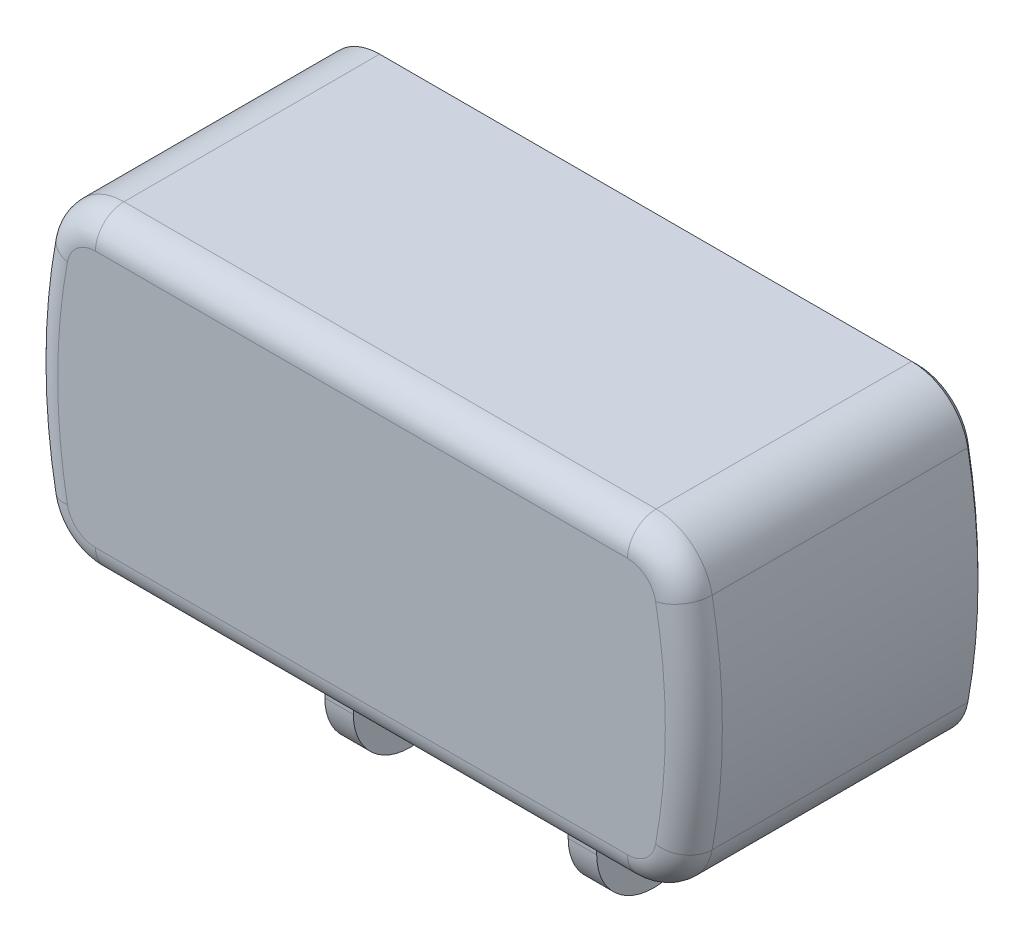
SolidWorks part; units mm, degrees
material "PLA"
ref_plane "Front Plane" through (0, 0, 0) normal (0, 0, 1) x (1, 0, 0)
ref_plane "Top Plane" through (0, 0, 0) normal (0, 1, 0) x (1, 0, 0)
ref_plane "Right Plane" through (0, 0, 0) normal (1, 0, 0) x (0, 0, -1)
sketch "Sketch2" plane through (0, 0, 0) normal (0, 0, 1) x (1, 0, 0)
  line L0 (-47.5, 0) -> (47.5, 0) construction
  line L1 (0, -27.5) -> (0, 27.5) construction
  line L2 (46.625, 27.5) -> (-46.625, 27.5)
  line L3 (46.625, -27.5) -> (-46.625, -27.5)
  arc A0 (-56.4565, 19.3279) -> (-56.4565, -19.3279) centre (47.5, 0) ccw
  arc A1 (-46.625, -27.5) -> (-56.4565, -19.3279) centre (-46.625, -17.5) cw
  arc A2 (-46.625, 27.5) -> (-56.4565, 19.3279) centre (-46.625, 17.5) ccw
  arc A3 (46.625, -27.5) -> (56.4565, -19.3279) centre (46.625, -17.5) ccw
  arc A4 (56.4565, 19.3279) -> (56.4565, -19.3279) centre (-47.5, 0) cw
  arc A5 (46.625, 27.5) -> (56.4565, 19.3279) centre (46.625, 17.5) cw
  point P4 (0, 0)
  point P8 (0, 0)
  dimension "D3" = 0
  dimension "D4" = 10
  dimension "D1" = 95
  dimension "D2" = 55
  dimension "D5" = 46.625
extrude "Boss-Extrude5" add sketch "Sketch2" along normal blind 50.8
fillet "Fillet9" radius 5 8 edges at (-58.238, 0, 50.8) (-53.0172, 25.1902, 50.8) (0, 27.5, 50.8) (53.0172, 25.1902, 50.8) (58.238, 0, 50.8) (53.0172, -25.1902, 50.8) (0, -27.5, 50.8) (-53.0172, -25.1902, 50.8)
sketch "Sketch3" plane through (0, 0, 0) normal (0, 0, -1) x (-1, 0, 0)
  line L0 (-55.738, 0) -> (55.738, 0) construction
  line L1 (0, 0) -> (0, 21.6868) construction
ref_plane "Plane1" through (-18.67, 0, 0) normal (1, 0, 0) x (0, 0, -1)
chamfer "Chamfer1" distance 1 angle 45 8 edges at (0, -27.5, 0) (53.0172, -25.1902, 0) (-53.0172, -25.1902, 0) (58.238, 0, 0) (-58.238, 0, 0) (53.0172, 25.1902, 0) (-53.0172, 25.1902, 0) (0, 27.5, 0)
sketch "Sketch8" plane through (18.825, 0, 0) normal (1, 0, 0) x (0, 0, -1)
  line L2 (-1, -27.5) -> (-45.8, -27.5)
  line L3 (-33.4051, -42.61) -> (-33.4051, -32.61)
  line L4 (-33.4137, -27.5) -> (-38.4137, -27.5)
  line L5 (-38.4137, -27.5) -> (-33.4051, -32.61)
  line L6 (-13.4051, -42.61) -> (-13.4051, -32.61)
  line L7 (-13.4051, -27.5) -> (-8.4051, -27.5)
  line L8 (-8.4051, -27.5) -> (-13.4051, -32.61)
  arc A0 (-33.4051, -42.61) -> (-13.4051, -42.61) centre (-23.4051, -42.61) ccw construction
  arc A2 (-33.4051, -42.61) -> (-13.4051, -42.61) centre (-23.4051, -42.61) ccw
  circle A4 centre (-23.4051, -35.61) radius 1.35
  circle A5 centre (-16.4051, -42.61) radius 1.35
  circle A6 centre (-23.4051, -49.61) radius 1.35
  circle A7 centre (-30.4051, -42.61) radius 1.35
  dimension "D1" = 2.7
  dimension "D2" = 10
  dimension "D3" = 5
  dimension "D4" = 5
extrude "Boss-Extrude6" add sketch "Sketch8" along normal blind 5
mirror "Mirror1" about plane through (0, 0, 0) normal (1, 0, 0) of "Boss-Extrude6"
sketch "Sketch4" plane through (0, 0, 0) normal (0, 0, -1) x (-1, 0, 0)
  line L1 (0, 27.5) -> (0, -27.5) construction
  line L3 (-46.625, 27.5) -> (46.625, 27.5) construction
  line L10 (46.625, -27.5) -> (-46.625, -27.5) construction
  line L11 (-58.238, 0) -> (58.238, 0) construction
  line L13 (-40.665, 14.165) -> (40.665, 14.165)
  line L14 (-45.665, 9.165) -> (-45.665, -9.165)
  line L15 (-40.665, -14.165) -> (40.665, -14.165)
  line L16 (45.665, 9.165) -> (45.665, -9.165)
  arc A0 (-56.4565, 19.3279) -> (-56.4565, -19.3279) centre (47.5, 0) ccw construction
  arc A1 (56.4565, -19.3279) -> (56.4565, 19.3279) centre (-47.5, 0) ccw construction
  arc A2 (40.665, -14.165) -> (45.665, -9.165) centre (40.665, -9.165) ccw
  arc A3 (-45.665, -9.165) -> (-40.665, -14.165) centre (-40.665, -9.165) ccw
  arc A4 (-40.665, 14.165) -> (-45.665, 9.165) centre (-40.665, 9.165) ccw
  arc A5 (40.665, 14.165) -> (45.665, 9.165) centre (40.665, 9.165) cw
  point P18 (0, 14.165)
  point P19 (-45.665, 0)
  point P24 (-45.665, -14.165)
  point P27 (-45.665, 14.165)
  point P30 (45.665, 14.165)
  dimension "D3" = 5
  dimension "D1" = 28.33
  dimension "D2" = 91.33
extrude "Cut-Extrude3" cut sketch "Sketch4" against normal blind 20
chamfer "Chamfer2" distance 20 angle 2 8 edges at (-45.665, 0, 20) (-44.2005, 12.7005, 20) (-44.2005, -12.7005, 20) (0, 14.165, 20) (0, -14.165, 20) (44.2005, 12.7005, 20) (44.2005, -12.7005, 20) (45.665, 0, 20) first distance on face at (-45.665, 0, 10) first distance on face at (-43.6828, 12.1828, 10) first distance on face at (-43.6828, -12.1828, 10) first distance on face at (0, 14.165, 10) first distance on face at (0, -14.165, 10) first distance on face at (43.6828, 12.1828, 10) first distance on face at (43.6828, -12.1828, 10) first distance on face at (45.665, 0, 10)
sketch "Sketch15" plane through (0, 0, 0) normal (0, 0, -1) x (-1, 0, 0)
  circle A0 centre (-48.2893, 18.5609) radius 1.35
  circle A2 centre (48.2893, -18.5609) radius 1.35
  circle A3 centre (48.2893, 18.5609) radius 1.35
  circle A4 centre (-48.2893, -18.5609) radius 1.35
  dimension "D1" = 2.7
extrude "Cut-Extrude4" cut sketch "Sketch15" against normal blind 5
sketch "Sketch16" plane through (0, -27.5, 0) normal (0, -1, 0) x (1, 0, 0)
  line L8 (22.7508, 1.8905) -> (22.7508, 4.5905)
  line L9 (19.9508, 7.3905) -> (11.1508, 7.3905)
  line L10 (8.3508, 4.5905) -> (8.3508, 1.8904)
  line L11 (11.1508, -0.9095) -> (19.9509, -0.9095)
  line L12 (22.7508, 1.8905) -> (22.7508, 4.5905)
  line L13 (19.9508, 7.3905) -> (11.1508, 7.3905)
  line L14 (8.3508, 4.5905) -> (8.3508, 1.8904)
  line L15 (11.1508, -0.9095) -> (19.9509, -0.9095)
  spline S8 degree 3 poles (-666.4959, 3939.094) (-77.2755, 305.6077) (-3.8508, -5.6751) (20.6762, -0.8202) (20.8544, -0.7664) (21.1919, -0.6259) (21.3528, -0.5406) (21.6575, -0.3367) (21.8009, -0.2187) (22.1882, 0.1676) (22.3971, 0.48) (22.6068, 0.985) (22.6607, 1.1623) (32.714, 51.4682) (-1349.1167, 276.3731) (-3923.1759, 650.9902) knots -16.850916 -16.850916 -16.850916 -16.850916 0.125 0.125 0.25 0.25 0.375 0.375 0.5 0.5 0.75 0.75 0.875 0.875 35.618041 35.618041 35.618041 35.618041 only from (19.9509, -0.9095) to (22.7508, 1.8905)
  spline S9 degree 3 poles (-3917.2496, -681.8391) (-283.7828, -92.6381) (27.5165, -19.2117) (22.6615, 5.3158) (22.6077, 5.494) (22.4672, 5.8315) (22.3819, 5.9925) (22.1781, 6.2971) (22.06, 6.4405) (21.6737, 6.8279) (21.3613, 7.0367) (20.8563, 7.2464) (20.679, 7.3003) (-29.5828, 17.3448) (-254.1468, -1362.0299) (-629.0518, -3938.5513) knots -16.851345 -16.851345 -16.851345 -16.851345 0.125 0.125 0.25 0.25 0.375 0.375 0.5 0.5 0.75 0.75 0.875 0.875 35.587364 35.587364 35.587364 35.587364 only from (22.7508, 4.5905) to (19.9508, 7.3905)
  spline S10 degree 3 poles (697.5949, -3932.5834) (108.3823, -299.1485) (34.9533, 12.1562) (10.4255, 7.3011) (10.2473, 7.2473) (9.9098, 7.1068) (9.7489, 7.0215) (9.4442, 6.8177) (9.3008, 6.6996) (8.9134, 6.3133) (8.7046, 6.001) (8.4949, 5.4959) (8.441, 5.3186) (-1.612, -44.9862) (1380.1581, -269.8822) (3954.2788, -644.5056) knots -16.851505 -16.851505 -16.851505 -16.851505 0.125 0.125 0.25 0.25 0.375 0.375 0.5 0.5 0.75 0.75 0.875 0.875 35.617291 35.617291 35.617291 35.617291 only from (11.1508, 7.3905) to (8.3508, 4.5905)
  spline S11 degree 3 poles (3948.4855, 688.3419) (314.8927, 99.121) (3.5851, 25.693) (8.4402, 1.1652) (8.494, 0.9869) (8.6345, 0.6494) (8.7198, 0.4885) (8.9236, 0.1838) (9.0417, 0.0404) (9.428, -0.3469) (9.7404, -0.5557) (10.2454, -0.7654) (10.4227, -0.8194) (60.6459, -10.8562) (284.9026, 1366.3859) (660.0361, 3945.0419) knots -16.851566 -16.851566 -16.851566 -16.851566 0.125 0.125 0.25 0.25 0.375 0.375 0.5 0.5 0.75 0.75 0.875 0.875 35.560649 35.560649 35.560649 35.560649 only from (8.3508, 1.8904) to (11.1508, -0.9095)
  spline S12 degree 3 poles (19.9509, -0.9095) (20.1357, -0.9095) (20.3176, -0.8912) (20.6762, -0.8202) (20.8544, -0.7664) (21.1919, -0.6259) (21.3528, -0.5406) (21.6575, -0.3367) (21.8009, -0.2187) (22.1882, 0.1676) (22.3971, 0.48) (22.6068, 0.985) (22.6607, 1.1623) (22.7328, 1.523) (22.7508, 1.7056) (22.7508, 1.8905) knots 0 0 0 0 0.125 0.125 0.25 0.25 0.375 0.375 0.5 0.5 0.75 0.75 0.875 0.875 1 1 1 1
  spline S13 degree 3 poles (22.7508, 4.5905) (22.7508, 4.7753) (22.7325, 4.9572) (22.6615, 5.3158) (22.6077, 5.494) (22.4672, 5.8315) (22.3819, 5.9925) (22.1781, 6.2971) (22.06, 6.4405) (21.6737, 6.8279) (21.3613, 7.0367) (20.8563, 7.2464) (20.679, 7.3003) (20.3183, 7.3724) (20.1357, 7.3905) (19.9508, 7.3905) knots 0 0 0 0 0.125 0.125 0.25 0.25 0.375 0.375 0.5 0.5 0.75 0.75 0.875 0.875 1 1 1 1
  spline S14 degree 3 poles (11.1508, 7.3905) (10.966, 7.3905) (10.7841, 7.3721) (10.4255, 7.3011) (10.2473, 7.2473) (9.9098, 7.1068) (9.7489, 7.0215) (9.4442, 6.8177) (9.3008, 6.6996) (8.9134, 6.3133) (8.7046, 6.001) (8.4949, 5.4959) (8.441, 5.3186) (8.3689, 4.9579) (8.3509, 4.7753) (8.3508, 4.5905) knots 0 0 0 0 0.125 0.125 0.25 0.25 0.375 0.375 0.5 0.5 0.75 0.75 0.875 0.875 1 1 1 1
  spline S15 degree 3 poles (8.3508, 1.8904) (8.3509, 1.7057) (8.3692, 1.5237) (8.4402, 1.1652) (8.494, 0.9869) (8.6345, 0.6494) (8.7198, 0.4885) (8.9236, 0.1838) (9.0417, 0.0404) (9.428, -0.3469) (9.7404, -0.5557) (10.2454, -0.7654) (10.4227, -0.8194) (10.7834, -0.8915) (10.966, -0.9095) (11.1508, -0.9095) knots 0 0 0 0 0.125 0.125 0.25 0.25 0.375 0.375 0.5 0.5 0.75 0.75 0.875 0.875 1 1 1 1
  dimension "D1" = 0.5
extrude "Cut-Extrude5" cut sketch "Sketch16" against normal up to surface (13.3032 mm away) up to face at (0, -13.8158, 10)
